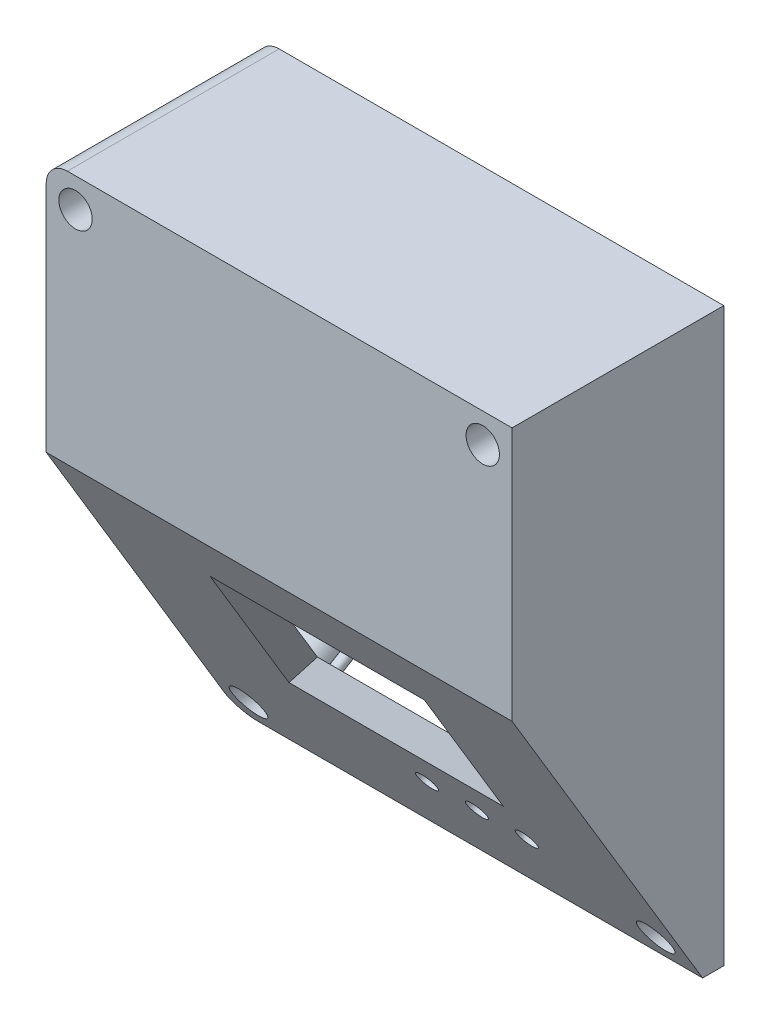
SolidWorks part; units mm, degrees
ref_plane "Front Plane" through (0, 0, 0) normal (0, 0, 1) x (1, 0, 0)
ref_plane "Top Plane" through (0, 0, 0) normal (0, 1, 0) x (1, 0, 0)
ref_plane "Right Plane" through (0, 0, 0) normal (1, 0, 0) x (0, 0, -1)
sketch "Sketch1" plane through (0, 0, 0) normal (0, 0, 1) x (1, 0, 0)
  line L0 (-92.5, 50) -> (-92.5, -50) construction
  line L1 (-4.5, 54) -> (-88.5, 54)
  line L2 (-4.5, 54) -> (-4.5, -54)
  line L3 (-4.5, -54) -> (-88.5, -54)
  line L4 (-92.5, 50) -> (-92.5, -50)
  line L5 (-88.5, -54) -> (-4.5, -54) construction
  arc A0 (-88.5, 54) -> (-92.5, 50) centre (-88.5, 50) ccw
  arc A1 (-88.5, -54) -> (-92.5, -50) centre (-88.5, -50) cw
  point P13 (-92.5, -54)
  dimension "D1" = 4
extrude "Boss-Extrude1" add sketch "Sketch1" along normal blind 40
sketch "Sketch2" plane through (-92.5, 0, 0) normal (-1, 0, 0) x (0, 0, 1)
  line L0 (40, -54) -> (40, 6)
  line L1 (40, 50) -> (40, -50) construction
  line L2 (40, 6) -> (4, -54)
  line L3 (40, -54) -> (0, -54) construction
  line L4 (4, -54) -> (40, -54)
  line L10 (0, -50) -> (0, -54) construction
  line M9 (0, -50) -> (40, -50)
  line M10 (40, -50) -> (40, 50)
  dimension "D1" = 60
  dimension "D2" = 4
extrude "Cut-Extrude1" cut sketch "Sketch2" against normal up to surface (88 mm away) contours L2 M10 M9 | L2 L4 L0 M9 region at (-92.5, -52.023, 22.5931) region at (-92.5, -31.3333, 28.8) up to face at (-4.5, 0, 20)
shell "Shell1" thickness 4 removed face at (-62.1095, 0, 0)
sketch "Sketch3" plane through (0, 0, 0) normal (0, 0, 1) x (1, 0, 0)
  circle A0 centre (-86.962, 48.462) radius 4.175
  circle A1 centre (-10.038, 48.462) radius 4.175
  circle A2 centre (-86.962, -48.462) radius 4.175
  circle A3 centre (-10.038, -48.462) radius 4.175
  arc A4 (-88.5, 44.5806) -> (-83.0806, 50) centre (-86.962, 48.462) ccw construction
  arc A5 (-13.9194, 50) -> (-8.5, 44.5806) centre (-10.038, 48.462) ccw construction
  arc A6 (-83.0806, -50) -> (-88.5, -44.5806) centre (-86.962, -48.462) ccw construction
  arc A7 (-8.5, -44.5806) -> (-13.9194, -50) centre (-10.038, -48.462) ccw construction
extrude "Boss-Extrude2" add sketch "Sketch3" along normal up to surface (7.3228 mm away) contours A2 | A3 up to face at (-56.6657, -29.3657, 18.7806)
extrude "Boss-Extrude3" add sketch "Sketch3<3>" along normal up to surface (40 mm away) contours A0 | A1 up to face at (-56.6657, 34.1657, 40)
sketch "Sketch3<3>" plane through (0, 0, 0) normal (0, 0, 1) x (1, 0, 0) same geometry as "Sketch3"
sketch "Sketch4" plane through (0, 0, 40) normal (0, 0, 1) x (1, 0, 0)
  circle A0 centre (-86.962, 48.462) radius 3.15
  arc A1 (-88.5, 44.5806) -> (-83.0806, 50) centre (-86.962, 48.462) ccw construction
  circle A2 centre (-10.038, 48.462) radius 3.15
  circle A3 centre (-10.038, -48.462) radius 3.15
  circle A4 centre (-86.962, -48.462) radius 3.15
  arc A5 (-13.9194, 50) -> (-8.5, 44.5806) centre (-10.038, 48.462) ccw construction
  arc A6 (-83.0806, -50) -> (-88.5, -44.5806) centre (-86.962, -48.462) ccw construction
  arc A7 (-8.5, -44.5806) -> (-13.9194, -50) centre (-10.038, -48.462) ccw construction
  circle A8 centre (-86.962, 48.462) radius 1.575
  circle A9 centre (-10.038, 48.462) radius 1.575
  circle A10 centre (-10.038, -48.462) radius 1.575
  circle A11 centre (-86.962, -48.462) radius 1.575
  dimension "D1" = 6.3
  dimension "D2" = 3.15
extrude "Cut-Extrude2" cut sketch "Sketch4" against normal up to surface (40 mm away) contours A8 | A9 | A10 | A11 up to face at (-48.5, 0, 0)
extrude "Cut-Extrude3" cut sketch "Sketch4<3>" against normal offset from surface (38.5 mm away) 1.5 up to face at (-88.537, -48.462, 0)
sketch "Sketch4<3>" plane through (0, 0, 40) normal (0, 0, 1) x (1, 0, 0) same geometry as "Sketch4"
sketch "Sketch5" plane through (0, -14.0008, 23.3347) normal (0, 0.5145, -0.8575) x (-1, 0, 0)
  circle A0 centre (79, -30.6712) radius 4.675
  circle A1 centre (18, -30.6712) radius 4.675
  circle A2 centre (79, 14.3288) radius 4.675
  circle A3 centre (18, 14.3288) radius 4.675
  circle A4 centre (79, 14.3288) radius 2.175
  circle A5 centre (18, 14.3288) radius 2.175
  circle A6 centre (18, -30.6712) radius 2.175
  circle A7 centre (79, -30.6712) radius 2.175
  circle A8 centre (79, -30.6712) radius 1.6 construction
  circle A9 centre (18, -30.6712) radius 1.6 construction
  circle A11 centre (79, 14.3288) radius 1.6 construction
  circle A12 centre (18, 14.3288) radius 1.6 construction
  dimension "D1" = 4.35
  dimension "D2" = 2.5
extrude "Boss-Extrude4" add sketch "Sketch5" along normal blind 7.5
sketch "Sketch10" plane through (0, -14.0008, 23.3347) normal (0, 0.5145, -0.8575) x (-1, 0, 0)
  circle A0 centre (63.74, -16.7859) radius 1
  circle A1 centre (33.26, -16.7859) radius 1
  circle A2 centre (63.74, 11.1541) radius 1
  circle A3 centre (33.26, 11.1541) radius 1
  circle A5 centre (63.74, -16.7859) radius 1.25 construction
  point P9 (33.26, -16.8254)
  point P10 (63.74, 11.1541)
  point P11 (33.26, 11.1541)
  point P12 (63.74, -16.7859)
  dimension "D1" = 0.25
extrude "Boss-Extrude8" add sketch "Sketch10" along normal up to surface (7.5 mm away) up to face at (-79, -32.4337, 3.5286)
sketch "Sketch11" plane through (0, -16.0588, 26.7647) normal (0, -0.5145, 0.8575) x (1, 0, 0)
  line L1 (-64.75, -13.2529) -> (-32.25, -13.2529)
  line L2 (-64.75, -13.2529) -> (-64.75, 7.7471)
  line L3 (-64.75, 7.7471) -> (-32.25, 7.7471)
  line L4 (-32.25, -13.2529) -> (-32.25, 7.7471)
  line L5 (-64.75, -13.2529) -> (-32.25, 7.7471) construction
  line L6 (-64.75, 7.7471) -> (-32.25, -13.2529) construction
  line L7 (-31.25, 8.7471) -> (-65.75, 8.7471) construction
  line L8 (-65.75, 8.7471) -> (-65.75, -14.2529) construction
  point P0 (-48.5, -2.7529)
  point P9 (-65.75, -2.7529)
  point P10 (-48.5, 8.7471)
  dimension "D1" = 1
  dimension "D2" = 1
extrude "Cut-Extrude6" cut sketch "Sketch11" against normal up to surface (4 mm away) up to face at (-33.26, -3.5788, 29.5879)
chamfer "Chamfer2" distance 4 angle 45 4 edges at (-48.5, -27.4231, 19.9461) (-32.25, -18.4194, 25.3483) (-48.5, -9.4158, 30.7505) (-64.75, -18.4194, 25.3483)
sketch "Sketch12" plane through (0, -16.0588, 26.7647) normal (0, -0.5145, 0.8575) x (1, 0, 0)
  circle A0 centre (-47.45, -26.5212) radius 1.95
  circle A1 centre (-37.95, -26.4212) radius 1.95
  circle A2 centre (-28.55, -26.4212) radius 1.95
  circle A3 centre (-47.45, -26.5212) radius 1.65 construction
  circle A4 centre (-37.95, -26.4212) radius 1.65 construction
  circle A5 centre (-28.55, -26.4212) radius 1.65 construction
  point P6 (-47.4698, -26.9922)
  dimension "D1" = 0.3
extrude "Cut-Extrude7" cut sketch "Sketch12" against normal up to surface (4 mm away) up to face at (-48.5, -16.3615, 21.9184)
